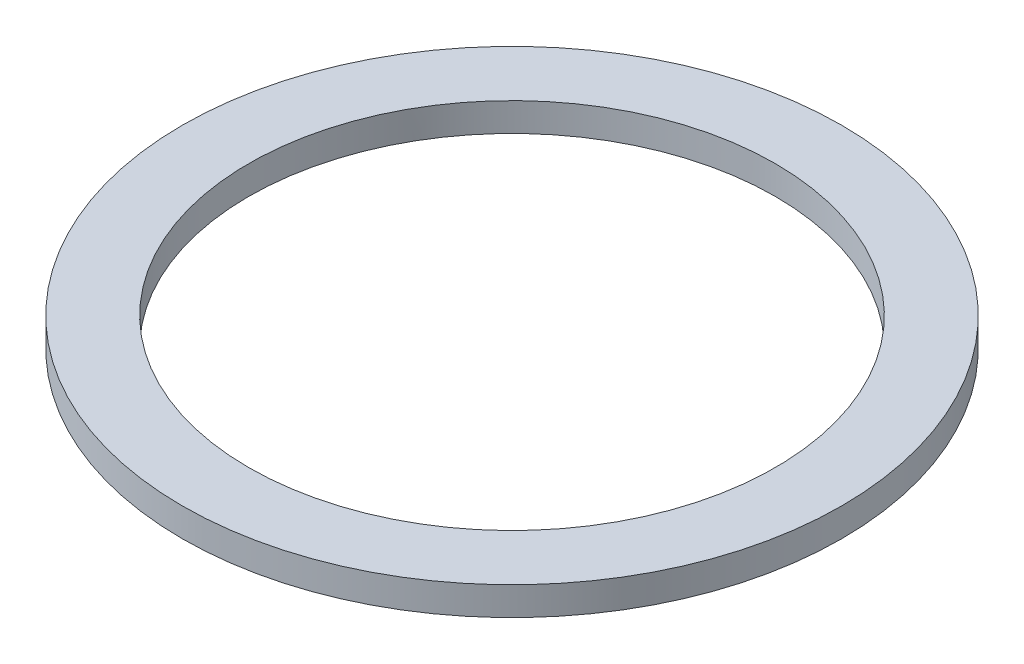
SolidWorks part; units mm, degrees
ref_plane "Front Plane" through (0, 0, 0) normal (0, 0, 1) x (1, 0, 0)
ref_plane "Top Plane" through (0, 0, 0) normal (0, 1, 0) x (1, 0, 0)
ref_plane "Right Plane" through (0, 0, 0) normal (1, 0, 0) x (0, 0, -1)
sketch "Sketch1" plane through (0, 0, 0) normal (0, 0, 1) x (1, 0, 0)
  line L0 (55, 0) -> (-55, 0) construction
  line L2 (111, 12) -> (139, 12)
  line L3 (111, 12) -> (111, 0)
  line L4 (111, 0) -> (117.0627, 0)
  line L5 (139, 12) -> (139, 0)
  line L6 (111, 12) -> (139, 0) construction
  line L7 (111, 0) -> (139, 12) construction
  line L8 (0, -55) -> (0, 55) construction
  line L9 (0, 4.511) -> (0, 20.439) construction
  line L12 (139, 0) -> (132.9373, 0)
  arc A0 (117.0627, 0) -> (132.9373, 0) centre (125, -1) cw
  point P0 (125, 6)
  point P4 (111, 6)
  dimension "D3" = 8
  dimension "D1" = 111
  dimension "D2" = 28
  dimension "D4" = 12
  dimension "D5" = 1
  dimension "D6" = 14
revolve "Revolve1" add sketch "Sketch1" angle 360 about L9
sketch "Sketch2" plane through (0, 0, 0) normal (0, -1, 0) x (1, 0, 0)
  line L0 (82.7344, 57.9312) -> (90.9259, 63.667)
  line L1 (87.4686, 50.5) -> (96.1288, 55.5)
  line L2 (55, 0) -> (-55, 0) construction
  arc A0 (87.4686, 50.5) -> (82.7344, 57.9312) centre (0, 0) ccw
  arc A1 (96.1288, 55.5) -> (90.9259, 63.667) centre (0, 0) ccw
  dimension "D1" = 101
  dimension "D4" = 111
  dimension "D2" = 30
  dimension "D3" = 5
extrude "Boss-Extrude1" add sketch "Sketch2" against normal blind 4
pattern_circular "CirPattern2" count 2 every 55 about axis through (0, 0, 0) along (0, 1, 0) of "Boss-Extrude1"
sketch "Sketch3" plane through (0, 12, 0) normal (0, 1, 0) x (1, 0, 0)
  line L0 (0, 0) -> (0, -110.7826)
  line L1 (0, -55) -> (0, 55) construction
  line L2 (0, 0) -> (-74.6614, -82.1382)
  line L3 (-74.6614, -82.1382) -> (-10.1788, -72.7082)
  line L4 (-74.6614, -82.1382) -> (-96.7588, -94.0463)
  circle A0 centre (0, 0) radius 111 construction
  dimension "D1" = 42.27
  dimension "D2" = 39.41
  dimension "D3" = 160
sketch "Sketch5" plane through (0, 0, 0) normal (0, -1, 0) x (1, 0, 0)
  line L0 (-75.2472, 81.6019) -> (-79.6487, 83.9738)
  line L1 (-74.6614, 82.1382) -> (-96.7588, 94.0463) construction
  line L2 (-79.6487, 83.9738) -> (-78.9371, 85.2943)
  line L3 (-78.9371, 85.2943) -> (-74.0703, 82.6716)
  line L4 (-74.0703, 82.6716) -> (-71.8954, 81.4996)
  line L5 (-75.2472, 81.6019) -> (-72.607, 80.1791)
  line L6 (-72.607, 80.1791) -> (-71.8954, 81.4996)
  arc A0 (0, 111) -> (96.1288, 55.5) centre (0, 0) ccw construction
  dimension "D1" = 5
  dimension "D2" = 0.75
  dimension "D3" = 1.5
extrude "Cut-Extrude1" cut sketch "Sketch5" against normal blind 9
fillet "Fillet1" radius 14 2 edges at (85.1825, 4, 54.2673) (4.4056, 4, 100.9039)
equation "\"D6@Sketch1\"=\"D2@Sketch1\"/2"
